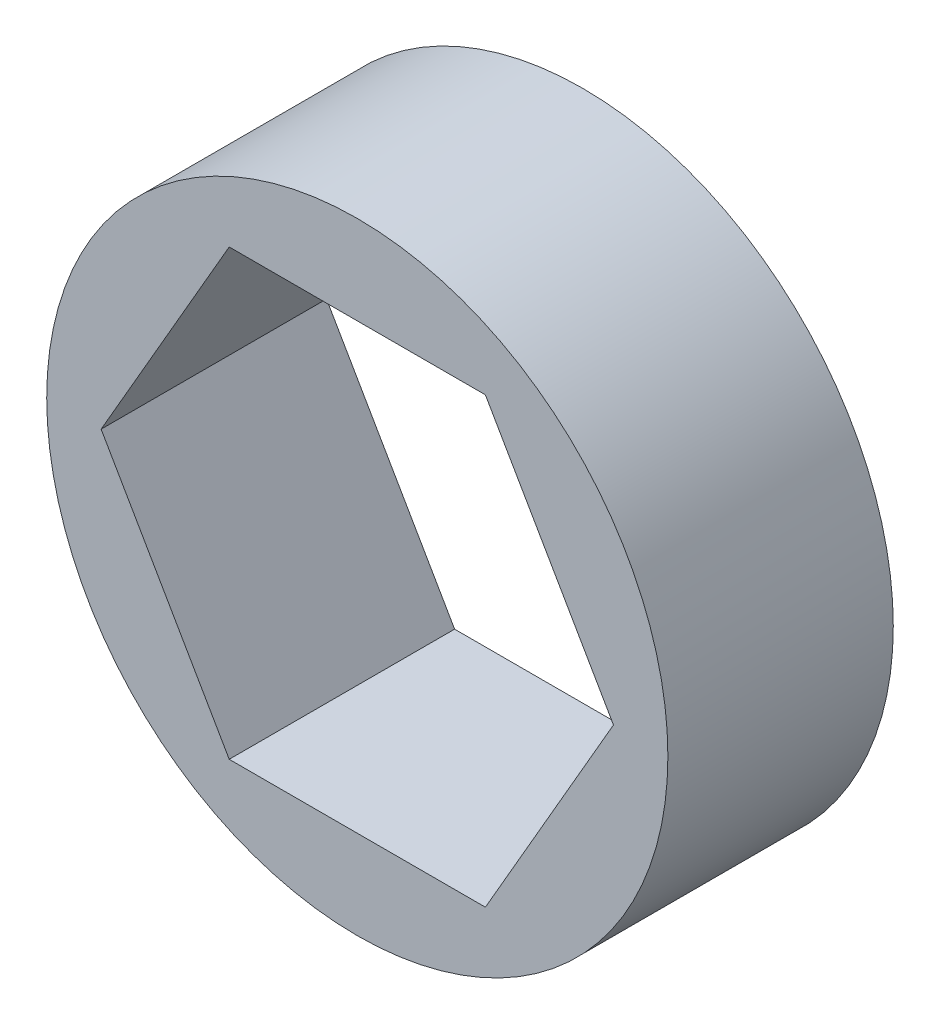
SolidWorks part; units mm, degrees
material "PET"
ref_plane "Front Plane" through (0, 0, 0) normal (0, 0, 1) x (1, 0, 0)
ref_plane "Top Plane" through (0, 0, 0) normal (0, 1, 0) x (1, 0, 0)
ref_plane "Right Plane" through (0, 0, 0) normal (1, 0, 0) x (0, 0, -1)
sketch "Sketch1" plane through (0, 0, 0) normal (0, 0, 1) x (1, 0, 0)
  line L1 (-7.3323, 0) -> (-3.6662, -6.35)
  line L2 (-3.6662, -6.35) -> (3.6662, -6.35)
  line L3 (3.6662, -6.35) -> (7.3323, 0)
  line L4 (7.3323, 0) -> (3.6662, 6.35)
  line L5 (3.6662, 6.35) -> (-3.6662, 6.35)
  line L6 (-3.6662, 6.35) -> (-7.3323, 0)
  circle A1 centre (0, 0) radius 8.89
  circle A2 centre (0, 0) radius 6.35 construction
  dimension "D1" = 17.78
  dimension "D2" = 12.7
extrude "Boss-Extrude1" add sketch "Sketch1" along normal mid plane 6.4516
